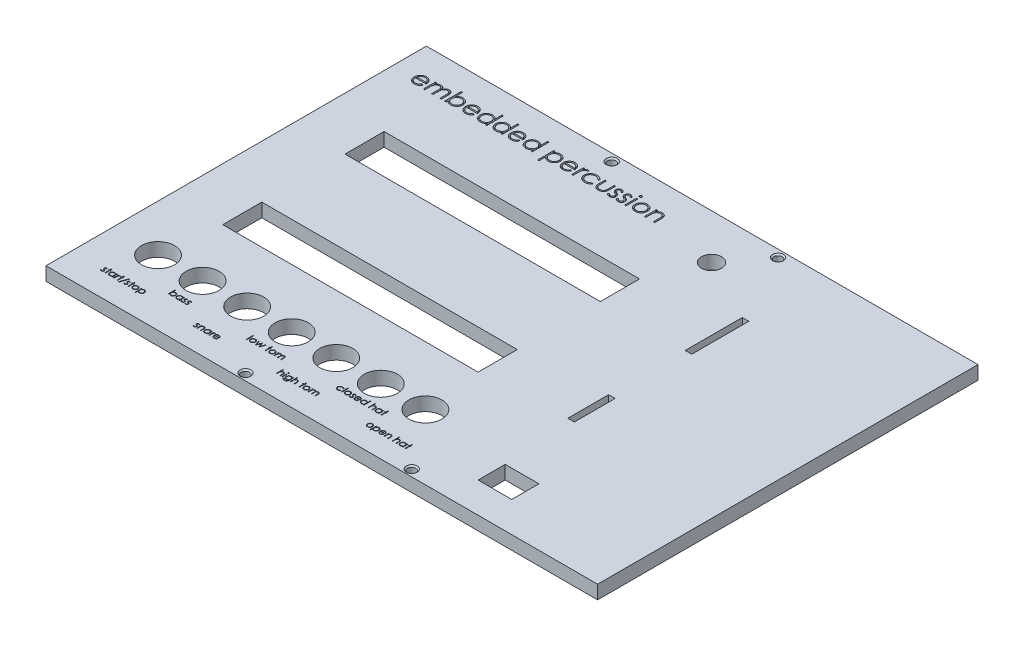
SolidWorks part; units mm, degrees
ref_plane "Front Plane" through (0, 0, 0) normal (0, 0, 1) x (1, 0, 0)
ref_plane "Top Plane" through (0, 0, 0) normal (0, 1, 0) x (1, 0, 0)
ref_plane "Right Plane" through (0, 0, 0) normal (1, 0, 0) x (0, 0, -1)
sketch "Sketch1" plane through (0, 0, 0) normal (0, 1, 0) x (1, 0, 0)
  line L0 (1.8101, -33.655) -> (1.8101, -144.145) construction
  line L1 (0, 0) -> (257.81, 0)
  line L2 (0, 0) -> (0, -177.8)
  line L3 (0, -177.8) -> (257.81, -177.8)
  line L4 (257.81, 0) -> (257.81, -177.8)
  line L5 (1.8101, -144.145) -> (166.9101, -144.145) construction
  line L6 (166.9101, -144.145) -> (166.9101, -33.655) construction
  line L7 (166.9101, -33.655) -> (1.8101, -33.655) construction
  line L8 (166.9101, -6.35) -> (166.9101, -171.45) construction
  line L9 (166.9101, -171.45) -> (219.2976, -171.45) construction
  line L10 (219.2976, -171.45) -> (219.2976, -6.35) construction
  line L11 (219.2976, -6.35) -> (166.9101, -6.35) construction
  line L12 (84.3601, -33.655) -> (84.3601, -144.145) construction
  line L17 (24.6701, -44.45) -> (144.0501, -44.45)
  line L18 (24.6701, -44.45) -> (24.6701, -62.738)
  line L19 (24.6701, -62.738) -> (144.0501, -62.738)
  line L20 (144.0501, -44.45) -> (144.0501, -62.738)
  line L21 (24.6701, -101.6) -> (144.0501, -101.6)
  line L22 (24.6701, -101.6) -> (24.6701, -119.888)
  line L23 (24.6701, -119.888) -> (144.0501, -119.888)
  line L24 (144.0501, -101.6) -> (144.0501, -119.888)
  line L25 (187.706, -150.876) -> (203.454, -150.876)
  line L26 (187.706, -150.876) -> (187.706, -163.576)
  line L27 (187.706, -163.576) -> (203.454, -163.576)
  line L28 (203.454, -150.876) -> (203.454, -163.576)
  line L29 (84.3601, -147.32) -> (0, -147.32) construction
  line L30 (84.3601, -147.32) -> (166.9101, -147.32) construction
  line L32 (186.7221, -36.0378) -> (183.6741, -36.0378)
  line L33 (186.7221, -36.0378) -> (186.7221, -62.7078)
  line L34 (186.7221, -62.7078) -> (183.6741, -62.7078)
  line L35 (183.6741, -36.0378) -> (183.6741, -62.7078)
  line L36 (186.7221, -98.5218) -> (183.6741, -98.5218)
  line L37 (186.7221, -98.5218) -> (186.7221, -117.5718)
  line L38 (186.7221, -117.5718) -> (183.6741, -117.5718)
  line L39 (183.6741, -98.5218) -> (183.6741, -117.5718)
  circle A1 centre (21.8761, -147.32) radius 7.747
  circle A2 centre (42.7041, -147.32) radius 7.747
  circle A3 centre (84.3601, -147.32) radius 7.747
  circle A4 centre (126.0161, -147.32) radius 7.747
  circle A5 centre (146.8441, -147.32) radius 7.747
  circle A6 centre (63.5321, -147.32) radius 7.747
  circle A7 centre (105.1881, -147.32) radius 7.747
  circle A8 centre (154.2101, -20.955) radius 4.699
  point P7 (166.9101, -88.9)
  point P14 (219.2976, -88.9)
  point P33 (84.3601, -44.45)
  point P34 (84.3601, -101.6)
  dimension "D22" = 15.494
  dimension "D23" = 15.494
  dimension "D24" = 15.494
  dimension "D25" = 15.494
  dimension "D26" = 15.494
  dimension "D27" = 15.494
  dimension "D28" = 15.494
  dimension "D38" = 9.398
  dimension "D1" = 257.81
  dimension "D2" = 177.8
  dimension "D3" = 165.1
  dimension "D4" = 110.49
  dimension "D5" = 52.3875
  dimension "D6" = 165.1
  dimension "D7" = 0
  dimension "D8" = 19.05
  dimension "D9" = 3.048
  dimension "D10" = 3.048
  dimension "D11" = 6.35
  dimension "D12" = 26.67
  dimension "D13" = 38.5124
  dimension "D14" = 119.38
  dimension "D15" = 119.38
  dimension "D16" = 18.288
  dimension "D17" = 18.288
  dimension "D18" = 38.862
  dimension "D19" = 38.1
  dimension "D20" = 12.7
  dimension "D21" = 15.748
  dimension "D29" = 30.48
  dimension "D30" = 20.828
  dimension "D31" = 20.828
  dimension "D32" = 20.828
  dimension "D33" = 20.828
  dimension "D34" = 20.828
  dimension "D35" = 20.828
  dimension "D36" = 16.764
  dimension "D37" = 16.764
  dimension "D39" = 12.7
  dimension "D40" = 12.7
  dimension "D41" = 14.224
  dimension "D42" = 54.356
  dimension "D43" = 35.814
  dimension "D44" = 36.0378
extrude "Boss-Extrude1" add sketch "Sketch1" along normal blind 6.35
sketch "Sketch2" plane through (0, 6.35, 0) normal (0, 1, 0) x (1, 0, 0)
  text T0 "embedded percussion" font "Century Gothic" height 7.62
extrude "Cut-Extrude1" cut sketch "Sketch2" against normal blind 1.27
sketch "Sketch3" plane through (0, 6.35, 0) normal (0, 1, 0) x (1, 0, 0)
  line L0 (16.51, -7.62) -> (13.2896, -14.5261)
  line L1 (13.2896, -14.5261) -> (4.3996, -14.5261)
  line L2 (4.3996, -14.5261) -> (11.2098, -20.2404)
  line L3 (11.2098, -20.2404) -> (8.9089, -28.8275)
  line L4 (8.9089, -28.8275) -> (16.7681, -24.6724)
  line L5 (16.7681, -24.6724) -> (24.9059, -28.2512)
  line L6 (24.9059, -28.2512) -> (21.9243, -19.8761)
  line L7 (21.9243, -19.8761) -> (27.3504, -14.5261)
  line L8 (27.3504, -14.5261) -> (19.7304, -14.5261)
  line L9 (19.7304, -14.5261) -> (16.51, -7.62)
  line L10 (16.51, 0) -> (16.51, -177.8) construction
  line L11 (257.81, 0) -> (0, 0) construction
  line L12 (0, -177.8) -> (257.81, -177.8) construction
  line L13 (0, 0) -> (0, -177.8) construction
  dimension "D1" = 8.89
  dimension "D2" = 7.62
  dimension "D3" = 8.89
  dimension "D4" = 7.62
  dimension "D5" = 8.89
  dimension "D6" = 8.89
  dimension "D7" = 8.89
  dimension "D8" = 40
  dimension "D9" = 115
  dimension "D10" = 8.89
  dimension "D11" = 7.62
  dimension "D12" = 7.62
  dimension "D13" = 16.51
  dimension "D14" = 7.62
  dimension "D15" = 25
  dimension "D16" = 25
  dimension "D17" = 66.262
  dimension "D18" = 115
sketch "Sketch5" plane through (0, 6.35, 0) normal (0, 1, 0) x (1, 0, 0)
  text T0 "bass"
  text T1 "snare"
  text T2 "low tom"
  text T3 "high tom"
  text T4 "closed hat"
  text T5 "open hat"
  text T6 "start/stop"
extrude "Cut-Extrude3" cut sketch "Sketch5" against normal blind 1.27
sketch "Sketch6" plane through (0, 6.35, 0) normal (0, 1, 0) x (1, 0, 0)
  line L0 (0, -3.4129) -> (257.81, -3.4129) construction
  line L1 (0, 0) -> (0, -177.8) construction
  line L2 (257.81, -177.8) -> (257.81, 0) construction
  line L3 (0, -174.625) -> (257.81, -174.625) construction
  line L4 (257.81, 0) -> (0, 0) construction
  line L5 (0, -177.8) -> (257.81, -177.8) construction
  line L6 (90.043, 0) -> (90.043, -177.8) construction
  line L7 (167.767, 0) -> (167.767, -177.8) construction
  point P16 (90.043, -3.4129)
  point P17 (167.767, -3.4129)
  point P18 (167.767, -174.625)
  point P19 (90.043, -174.625)
  dimension "D1" = 3.4129
  dimension "D2" = 3.175
  dimension "D3" = 90.043
  dimension "D4" = 90.043
hole_wizard "#6 Clearance Hole1" positions "Sketch7" profile "Sketch8" hole size "#6" standard "ANSI Inch" end condition through all
sketch "Sketch7" plane through (0, 6.35, 0) normal (0, 1, 0) x (1, 0, 0)
  point P0 (90.043, -3.4129)
  point P3 (167.767, -3.4129)
  point P6 (90.043, -174.625)
  point P9 (167.767, -174.625)
sketch "Sketch8" plane through (90.043, 6.35, 3.4129) normal (1, 0, 0) x (0, 0, 1)
  line L0 (0, 0) -> (0, 6.35)
  line L1 (0, 6.35) -> (1.8986, 6.35)
  line L2 (1.8986, 6.35) -> (1.8986, 0.635)
  line L3 (1.8986, 0.635) -> (2.5337, 0)
  line L5 (2.5337, 0) -> (0, 0)
  line L6 (-1.8986, 0.635) -> (-2.5337, 0) construction
  line L11 (0, -6.35) -> (0, 107.95) construction
  dimension "Thru Hole Dia." = 3.7973
  dimension "Thru Hole Depth" = 6.35
  dimension "Near C'Sink Dia." = 5.0673
  dimension "Near C'Sink Angle" = 90
